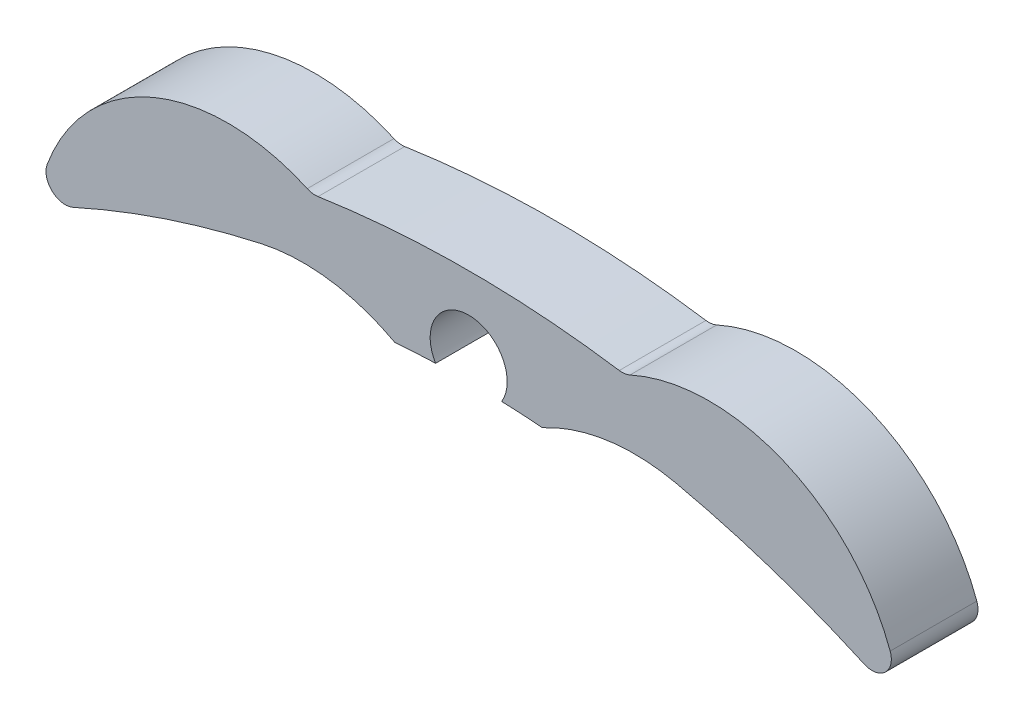
SolidWorks part; units mm, degrees
ref_plane "Front Plane" through (0, 0, 0) normal (0, 0, 1) x (1, 0, 0)
ref_plane "Top Plane" through (0, 0, 0) normal (0, 1, 0) x (1, 0, 0)
ref_plane "Right Plane" through (0, 0, 0) normal (1, 0, 0) x (0, 0, -1)
sketch "Sketch1" plane through (0, 0, 0) normal (0, 0, 1) x (1, 0, 0)
  line L0 (0, 6.155) -> (0, -19.5803) construction
  arc A0 (1.7155, -1.0281) -> (-1.7155, -1.0281) centre (0, 0) ccw
  circle A1 centre (0, -48.845) radius 55 construction
  arc A2 (-8.1179, 3.3728) -> (-22.4522, -6.5922) centre (-12.5, -5.616) ccw
  arc A3 (22.4522, -6.5922) -> (8.1179, 3.3728) centre (12.5, -5.616) ccw
  arc A4 (8.1179, 3.3728) -> (-8.1179, 3.3728) centre (0, -48.845) ccw
  arc A5 (22.4522, -6.5922) -> (1.7155, -1.0281) centre (0, -48.845) ccw
  arc A6 (-1.7155, -1.0281) -> (-22.4522, -6.5922) centre (0, -48.845) ccw
  point P12 (0, 4)
  point P16 (0, 2)
  point P17 (0, -1)
  dimension "D1" = 4
  dimension "D2" = 110
  dimension "D3" = 20
  dimension "D4" = 25
  dimension "D5" = 2
  dimension "D6" = 2.155
  dimension "D7" = 1
extrude "Boss-Extrude1" add sketch "Sketch1" along normal blind 4.5
sketch "Sketch2" plane through (0, 0, 4.5) normal (0, 0, 1) x (1, 0, 0)
  arc A0 (-3.9088, 0.8492) -> (3.9088, 0.8492) centre (0, -48.845) ccw
  circle A1 centre (0, -48.845) radius 47.8477 construction
  arc A2 (-1.7155, -1.0281) -> (-22.4522, -6.5922) centre (0, -48.845) ccw construction
  arc A3 (-3.9088, 0.8492) -> (3.9088, 0.8492) centre (0, 0) ccw
  arc A4 (8.1179, 3.3728) -> (-8.1179, 3.3728) centre (0, -48.845) ccw construction
  point P3 (0, 1.0027)
  point P8 (0, -0.9973)
  dimension "D1" = 2
extrude "Cut-Extrude1" cut sketch "Sketch2" against normal through all
fillet "Fillet1" radius 10 2 edges at (3.9088, 0.8492, 2.25) (-3.9088, 0.8492, 2.25)
fillet "Fillet2" radius 1 4 edges at (8.1179, 3.3728, 2.25) (-8.1179, 3.3728, 2.25) (22.4159, -4.3217, 2.25) (-22.4159, -4.3217, 2.25)
